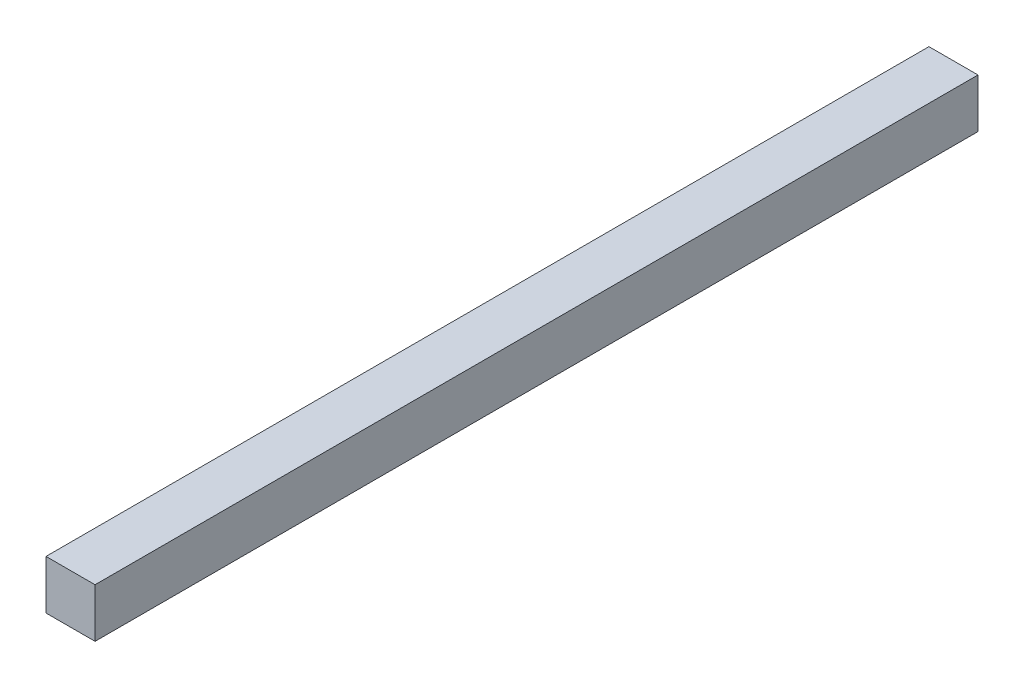
SolidWorks part; units mm, degrees
ref_plane "前视基准面" through (0, 0, 0) normal (0, 0, 1) x (1, 0, 0)
ref_plane "上视基准面" through (0, 0, 0) normal (0, 1, 0) x (1, 0, 0)
ref_plane "右视基准面" through (0, 0, 0) normal (1, 0, 0) x (0, 0, -1)
other "Configuration Table"
sketch "Sketch1" plane through (0, 0, 0) normal (0, 0, 1) x (1, 0, 0)
  line L1 (-20, -20) -> (20, -20)
  line L2 (-20, -20) -> (-20, 20)
  line L3 (-20, 20) -> (20, 20)
  line L4 (20, -20) -> (20, 20)
  line L5 (-20, -20) -> (20, 20) construction
  line L6 (-20, 20) -> (20, -20) construction
  point P0 (0, 0)
extrude "Boss-Extrude1" add sketch "Sketch1" along normal blind 720
ref_plane "top_face" through (0, 0, 720) normal (0, 0, 1) x (1, 0, 0)
ref_plane "inner_face_x_plus" through (20, 0, 0) normal (1, 0, 0) x (0, 0, -1)
ref_plane "inner_face_y_plus" through (0, 20, 0) normal (0, 1, 0) x (1, 0, 0)
sketch3d "3DSketch1"
  line L0 (0, 0, 0) -> (0, 0, 720) construction
ref_axis "center_axis_z" through (0, 0, 0) along (0, 0, 1)
